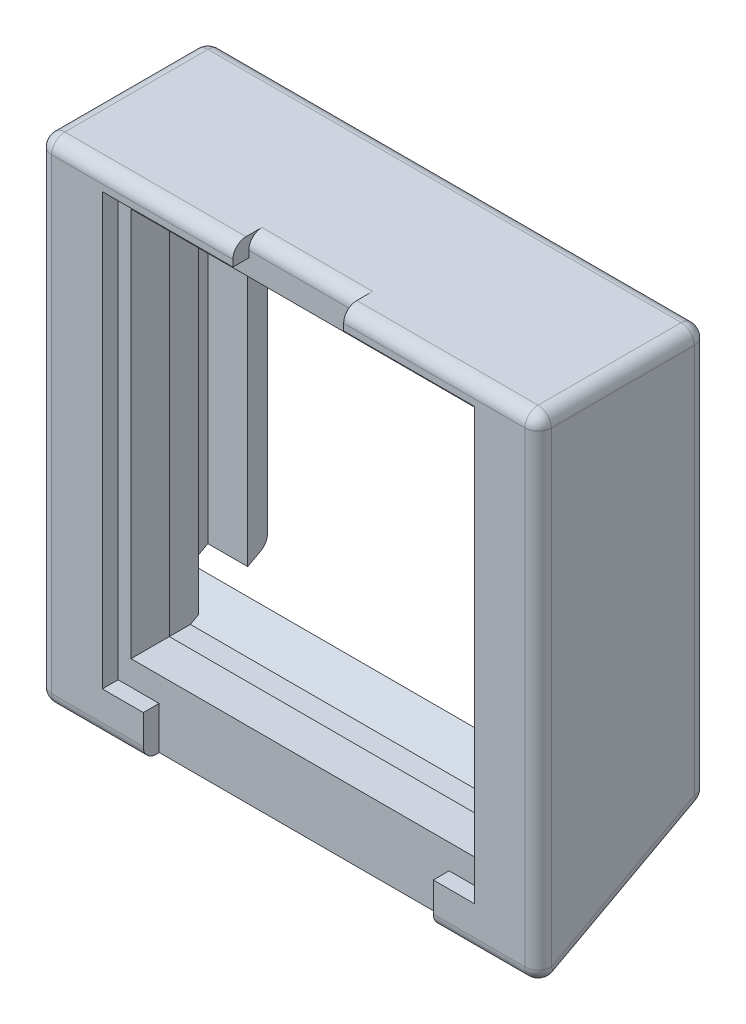
SolidWorks part; units mm, degrees
ref_plane "Front Plane" through (0, 0, 0) normal (0, 0, 1) x (1, 0, 0)
ref_plane "Top Plane" through (0, 0, 0) normal (0, 1, 0) x (1, 0, 0)
ref_plane "Right Plane" through (0, 0, 0) normal (1, 0, 0) x (0, 0, -1)
ref_plane "Plane1" through (0, -5.2304, -2.8169) normal (0, 0.8804, 0.4742) x (1, 0, 0)
ref_plane "Plane2" through (0, 25.335, 0) normal (0, 1, 0) x (1, 0, 0)
sketch "Sketch3" plane through (0, 0, 0) normal (0, 1, 0) x (1, 0, 0)
  line L0 (-14.43, 1.7) -> (-14.43, 0.2)
  line L1 (-14.43, 0.2) -> (-17.45, 0.2)
  line L2 (-17.45, 0.2) -> (-17.45, -1.85)
  line L3 (-17.45, -1.85) -> (-14.13, -1.85)
  line L6 (-14.13, -1.85) -> (-14.13, -6.35)
  line L7 (-14.13, -6.35) -> (-13.13, -6.35)
  line L8 (-13.13, -6.35) -> (-13.13, -9.95)
  line L9 (-13.13, -9.95) -> (-14.11, -9.95)
  line L10 (-14.11, -9.95) -> (-14.11, -11.15)
  line L11 (-14.11, -11.15) -> (-18.95, -11.15)
  line L12 (-18.95, -11.15) -> (-18.95, 1.7)
  line L13 (-18.95, 1.7) -> (-14.43, 1.7)
  line L14 (-17.25, 0) -> (17.25, 0) construction
  line L15 (-17.25, -1.65) -> (-17.25, 0) construction
  line L16 (-17.25, -1.65) -> (17.25, -1.65) construction
  line L17 (-13.91, -10.15) -> (13.91, -10.15) construction
  line L18 (-13.93, -4.65) -> (-13.93, -6.15) construction
  line L19 (-13.91, -11.65) -> (-13.91, -10.15) construction
  line L20 (-13.91, -11.65) -> (13.91, -11.65) construction
  line L21 (0, 0) -> (0, -15.6727) construction
  line L22 (18.95, 1.7) -> (14.43, 1.7)
  line L23 (18.95, -11.15) -> (18.95, 1.7)
  line L24 (14.11, -11.15) -> (18.95, -11.15)
  line L25 (14.11, -9.95) -> (14.11, -11.15)
  line L26 (13.13, -9.95) -> (14.11, -9.95)
  line L27 (13.13, -6.35) -> (13.13, -9.95)
  line L28 (14.13, -6.35) -> (13.13, -6.35)
  line L29 (14.13, -1.85) -> (14.13, -6.35)
  line L30 (17.45, -1.85) -> (14.13, -1.85)
  line L31 (17.45, 0.2) -> (17.45, -1.85)
  line L32 (14.43, 0.2) -> (17.45, 0.2)
  line L33 (14.43, 1.7) -> (14.43, 0.2)
  dimension "D1" = 0.2
  dimension "D2" = 0.2
  dimension "D3" = 0.2
  dimension "D6" = 0.2
  dimension "D7" = 0.2
  dimension "D8" = 0.2
  dimension "D9" = 0.2
  dimension "D10" = 0.5
  dimension "D11" = 1.5
  dimension "D12" = 1.5
  dimension "D13" = 0.5
  dimension "D4" = 0.8
extrude "Boss-Extrude1" add sketch "Sketch3" along normal up to surface (25.335 mm away) and the other way up to surface up to plane "Plane2" other way up to plane "Plane1"
sketch "Sketch4" plane through (0, 0, 0) normal (1, 0, 0) x (0, 0, -1)
  line L0 (1.7, 25.335) -> (-11.15, 25.335)
  line L1 (-11.15, 25.335) -> (-11.15, 23.835)
  line L2 (-11.15, 25.335) -> (-11.15, -12.7526) construction
  line L3 (-11.15, 23.835) -> (-9.95, 23.835)
  line L4 (-9.95, 25.335) -> (-9.95, -12.1063) construction
  line L5 (-9.95, 23.835) -> (-9.95, 22.59)
  line L6 (-9.95, 22.59) -> (-6.35, 22.59)
  line L7 (-6.35, 25.335) -> (-6.35, -10.1674) construction
  line L8 (-6.35, 22.59) -> (-6.35, 23.59)
  line L9 (-6.35, 25.335) -> (-6.35, -10.1674) construction
  line L14 (1.7, 25.335) -> (1.7, -5.8319) construction
  line L15 (1.7, 23.835) -> (1.7, 25.335)
  line L16 (-6.35, 23.59) -> (-1.85, 23.59)
  line L17 (-1.85, 23.59) -> (-1.85, 23.835)
  line L18 (-1.85, 23.835) -> (1.7, 23.835)
  line L20 (-6.15, 23.39) -> (-4.65, 23.39) construction
  line L21 (-1.65, 23.635) -> (0, 23.635) construction
  line L22 (-11.65, 23.635) -> (-10.15, 23.635) construction
  line L23 (-1.85, 25.335) -> (-1.85, -7.7439) construction
  line L24 (-11.15, -8.835) -> (-11.15, -12.7526)
  line L25 (-11.15, -12.7526) -> (-1.85, -7.7439)
  line L26 (-1.85, -7.7439) -> (-1.85, -6.5597)
  line L27 (-1.85, -6.5597) -> (-4.45, -7.96)
  line L28 (-4.45, -7.96) -> (-6.35, -7.96)
  line L29 (-6.35, -7.96) -> (-6.35, -6.96)
  line L30 (-6.35, -6.96) -> (-9.95, -6.96)
  line L31 (-9.95, -6.96) -> (-9.95, -8.835)
  line L32 (-9.95, 25.335) -> (-9.95, -12.1063) construction
  line L33 (-9.95, -8.835) -> (-11.15, -8.835)
  line L34 (-11.65, -8.635) -> (-10.15, -8.635) construction
  line L35 (-4.65, -7.76) -> (-6.15, -7.76) construction
  line L36 (-4.65, -7.76) -> (-4.65, -6.875) construction
  dimension "D1" = 0.2
  dimension "D2" = 0.2
  dimension "D6" = 0.2
  dimension "D8" = 0.2
  dimension "D9" = 0.2
  dimension "D4" = 0.8
  dimension "D5" = 0.2
  dimension "D7" = 0.8
extrude "Boss-Extrude2" add sketch "Sketch4" along normal up to surface and the other way up to surface up to face at (18.95, 8.0214, 4.725) other way up to face at (-18.95, 8.0214, 4.725)
fillet "Fillet1" radius 1 2 edges at (0, -7.7439, 1.85) (0, -12.7526, 11.15)
sketch "Sketch5" plane through (0, 0, 11.15) normal (0, 0, 1) x (1, 0, 0)
  line L0 (4.2, 23.635) -> (4.2, 24.135)
  line L1 (4.2, 24.135) -> (-4.2, 24.135) construction
  line L2 (-4.2, 24.135) -> (-4.2, 23.635)
  line L3 (-4.2, 23.635) -> (4.2, 23.635)
  line L4 (-4.2, 24.135) -> (-4.2, 25.335)
  line L5 (-18.95, 25.335) -> (18.95, 25.335) construction
  line L6 (-4.2, 25.335) -> (4.2, 25.335)
  line L7 (4.2, 25.335) -> (4.2, 24.135)
  line L8 (13.91, -8.635) -> (13.91, 23.635)
  line L9 (13.91, 23.635) -> (4, 23.635)
  line L10 (4, 23.635) -> (4, 23.935)
  line L11 (4, 23.935) -> (-4, 23.935)
  line L12 (-4, 23.935) -> (-4, 23.635)
  line L13 (-4, 23.635) -> (-13.91, 23.635)
  line L14 (-13.91, 23.635) -> (-13.91, -8.635)
  line L15 (-13.91, -8.635) -> (13.91, -8.635)
  line L16 (13.91, -8.635) -> (13.91, 23.635) construction
  line L17 (13.91, 23.635) -> (4, 23.635) construction
  line L18 (4, 23.635) -> (4, 23.935) construction
  line L19 (4, 23.935) -> (-4, 23.935) construction
  line L20 (-4, 23.935) -> (-4, 23.635) construction
  line L21 (-4, 23.635) -> (-13.91, 23.635) construction
  line L22 (-13.91, 23.635) -> (-13.91, -8.635) construction
  line L23 (-13.91, -8.635) -> (13.91, -8.635) construction
  line L24 (-11, -8.835) -> (-11, -12.0782)
  line L25 (14.11, -8.835) -> (-14.11, -8.835) construction
  line L26 (-11, -12.0782) -> (11, -12.0782)
  line L27 (-11, -8.835) -> (11, -8.835)
  line L28 (0, 0) -> (0, -15.5564) construction
  line L29 (-10, -8.635) -> (-10, -11.135) construction
  line L30 (-18.95, -12.0782) -> (18.95, -12.0782) construction
  line L31 (11, -8.835) -> (11, -12.0782)
  point P30 (0, -8.835)
  point P31 (0, -12.0782)
  dimension "D2" = 0.2
  dimension "D3" = 1
extrude "Cut-Extrude1" cut sketch "Sketch5" against normal up to surface (1.2 mm away) up to face at (0, 7.815, 9.95)
chamfer "Chamfer1" distance 0.7 angle 45 4 edges at (0, 22.59, 6.35) (13.13, 7.815, 6.35) (0, -6.96, 6.35) (-13.13, 7.815, 6.35)
chamfer "Chamfer2" distance 2 angle 45 3 edges at (-14.13, 8.5151, 1.85) (0, 23.59, 1.85) (14.13, 8.5151, 1.85)
fillet "Fillet2" radius 1 16 edges at (-18.95, -8.8953, 3.9879) (-18.95, -11.9367, 10.6628) (18.95, -8.8953, 3.9879) (18.95, -11.9367, 10.6628) (18.95, 25.335, 4.725) (11.575, 25.335, 11.15) (-11.575, 25.335, 11.15) (-18.95, 25.335, 4.725) (0, 25.335, -1.7) (-16.69, -5.8319, -1.7) (16.69, -5.8319, -1.7) (18.95, 9.7515, -1.7) (-18.95, 9.7515, -1.7) (-18.95, 7.1284, 11.15) (18.95, 7.1284, 11.15) (0, 25.335, 9.95)
sketch "Sketch6" plane through (0, 0, -1.7) normal (0, 0, -1) x (-1, 0, 0)
  line L0 (0, 26.6333) -> (0, 0) construction
  line L1 (2.54, 22.59) -> (-2.54, 22.59)
  line L2 (-2.54, 22.59) -> (-2.54, 25.335)
  line L3 (-2.54, 25.335) -> (2.54, 25.335)
  line L4 (-17.95, 25.335) -> (17.95, 25.335) construction
  line L6 (2.54, 22.59) -> (2.54, 25.335)
  line L7 (13.13, 22.59) -> (-13.13, 22.59) construction
  point P12 (0, 25.335)
  point P13 (0, 22.59)
  dimension "D1" = 2.54
equation "\"offset\"= .2mm"
equation "\"D1@Sketch3\"=\"offset\""
equation "\"D2@Sketch3\"=\"offset\""
equation "\"D3@Sketch3\"=\"offset\""
equation "\"D6@Sketch3\"=\"offset\""
equation "\"D7@Sketch3\"=\"offset\""
equation "\"D8@Sketch3\"=\"offset\""
equation "\"D9@Sketch3\"=\"offset\""
equation "\"D1@Plane2\"=1.5+\"offset\""
equation "\"led apnel overlap\"= .8"
equation "\"clearance\"=0.5"
equation "\"D1@Sketch4\"=\"offset\""
equation "\"D2@Sketch4\"=\"offset\""
equation "\"D4@Sketch4\"=\"led apnel overlap\""
equation "\"D5@Sketch4\"=\"offset\""
equation "\"D6@Sketch4\"=\"offset\""
equation "\"D7@Sketch4\"=\"led apnel overlap\""
equation "\"D8@Sketch4\"=\"offset\""
equation "\"D9@Sketch4\"=\"offset\""
equation "\"D2@Sketch5\"=\"offset\""
equation "\"D1@Sketch6\"=.1in"
